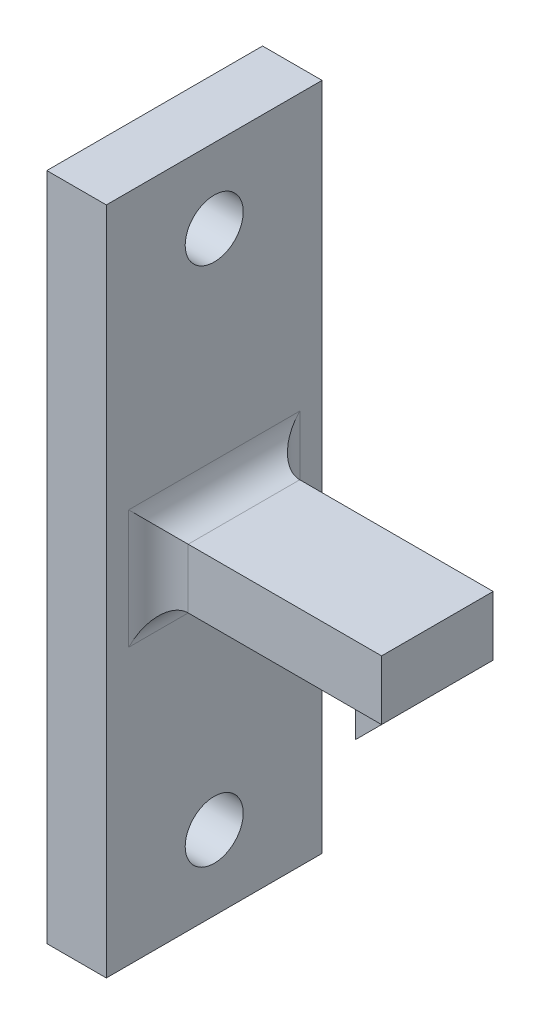
SolidWorks part; units mm, degrees
ref_plane "Front Plane" through (0, 0, 0) normal (0, 0, 1) x (1, 0, 0)
ref_plane "Top Plane" through (0, 0, 0) normal (0, 1, 0) x (1, 0, 0)
ref_plane "Right Plane" through (0, 0, 0) normal (1, 0, 0) x (0, 0, -1)
ref_plane "Plane1" through (0, 0, -2.5) normal (0, 0, 1) x (1, 0, 0)
sketch "Sketch2" plane through (0, 0, -2.5) normal (0, 0, 1) x (1, 0, 0)
  line L0 (230.0241, 2) -> (225.0241, 2)
  line L1 (225.0241, 2) -> (225.0241, -2)
  line L2 (225.0241, -2) -> (230.0241, -2)
  circle A0 centre (230.0241, 0) radius 1 construction
  circle A1 centre (230.0241, 0) radius 1
  circle A2 centre (230.0241, 0) radius 2
  dimension "D1" = 1
  dimension "D2" = 5
extrude "Boss-Extrude1" add sketch "Sketch2" along normal blind 1 and the other way blind 1 contours A2 L0 L1 L2 | A2 A1 region at (226.7677, 0, -2.5) region at (231.3983, 1.3742, -2.5)
sketch "Sketch3" plane through (0, 2, 0) normal (0, 1, 0) x (1, 0, 0)
  line L0 (225.0241, 1.5) -> (222.0241, -5.5)
  line L1 (222.0241, -5.5) -> (216.0955, -5.5)
  line L2 (216.0955, 10.5) -> (216.0955, 8.5)
  line L3 (216.0955, 10.5) -> (222.0241, 10.5)
  line L4 (225.0241, 3.5) -> (225.0241, 1.5)
  line L5 (225.0241, 1.5) -> (230.0241, 1.5)
  line L6 (230.0241, 1.5) -> (230.0241, 3.5)
  line L7 (230.0241, 3.5) -> (225.0241, 3.5)
  line L8 (225.0241, 3.5) -> (225.0241, 1.5)
  line L9 (225.0241, 1.5) -> (230.0241, 1.5)
  line L10 (230.0241, 1.5) -> (230.0241, 3.5)
  line L11 (230.0241, 3.5) -> (225.0241, 3.5)
  line L12 (222.0241, 10.5) -> (225.0241, 3.5)
  line L13 (216.0955, 8.5) -> (221.0955, 8.5)
  line L14 (221.0955, 8.5) -> (223.0241, 4)
  line L15 (223.0241, 4) -> (223.0241, 1)
  line L16 (230.0241, 2.5) -> (208.0852, 2.5) construction
  line L17 (139.7, 2.5) -> (266.7, 2.5) construction
  line L18 (216.0955, -5.5) -> (216.0955, -3.5)
  line L19 (221.0955, -3.5) -> (223.0241, 1)
  line L20 (216.0955, -3.5) -> (221.0955, -3.5)
  line M15 (225.0241, 3.5) -> (225.0241, 1.5)
  dimension "D2" = 2
  dimension "D3" = 5
  dimension "D4" = 2
  dimension "D5" = 7
  dimension "D6" = 3
  dimension "D7" = 3
  dimension "D1" = 0
extrude "Boss-Extrude2" add sketch "Sketch3" against normal up to surface (4 mm away) contours L16 L12 L3 L2 L13 L14 L15 M15 | L8 L16 L15 L19 L20 L18 L1 L0 region at (223.4139, 2, 1.9528) region at (224.0241, 2, -2.6199) up to face at (227.5241, -2, -2.5)
sketch "Sketch4" plane through (0, 0, -10.5) normal (0, 0, -1) x (-1, 0, 0)
  line L0 (-216.0955, 0) -> (-218.0955, 0)
  line L1 (-139.7, 0) -> (-266.7, 0) construction
  line L4 (-222.0241, -2) -> (-216.0955, -2)
  line L5 (-216.0955, -2) -> (-216.0955, 2)
  line L6 (-216.0955, 2) -> (-222.0241, 2)
  line L7 (-222.0241, 2) -> (-222.0241, -2)
  line L8 (-222.0241, -2) -> (-216.0955, -2)
  line L9 (-216.0955, -2) -> (-216.0955, 2)
  line L10 (-216.0955, 2) -> (-222.0241, 2)
  line L11 (-222.0241, 2) -> (-222.0241, -2)
  circle A0 centre (-218.0955, 0) radius 1.07
  dimension "D2" = 2.14
  dimension "D3" = 2
  dimension "D1" = 0
extrude "Cut-Extrude1" cut sketch "Sketch4" against normal through all contours A0 region at (219.1352, 0, -10.5)
sketch "Sketch6" plane through (0, 0, -1.5) normal (0, 0, 1) x (1, 0, 0)
  line L0 (230.0241, 2) -> (240.0241, 2)
  line L1 (240.0241, 2) -> (240.0241, -2)
  line L2 (240.0241, -2) -> (230.0241, -2)
  line L3 (230.0241, 2) -> (228.1025, 2)
  line L4 (230.0241, 2) -> (225.0241, 2) construction
  line L5 (228.1025, 2) -> (228.1025, -2)
  line L6 (225.0241, -2) -> (230.0241, -2) construction
  line L7 (228.1025, -2) -> (230.0241, -2)
  arc A0 (230.0241, -2) -> (230.0241, 2) centre (230.0241, 0) ccw construction
  dimension "D1" = 10
extrude "Boss-Extrude3" add sketch "Sketch6" against normal blind 2
sketch "Sketch8" plane through (0, 0, -3.5) normal (0, 0, -1) x (-1, 0, 0)
  line L0 (-240.0241, -2) -> (-236.0241, -6)
  line L1 (-240.0241, 2) -> (-236.0241, 2)
  line L2 (-240.0241, 2) -> (-240.0241, -6)
  line L3 (-240.0241, -6) -> (-236.0241, -6)
  line L4 (-236.0241, 2) -> (-236.0241, -6)
  dimension "D1" = 4
  dimension "D2" = 8
extrude "Boss-Extrude4" add sketch "Sketch8" against normal blind 2 contours L2 L1 L4 L3
sketch "Sketch9" plane through (0, 0, -3.5) normal (0, 0, -1) x (-1, 0, 0)
  line L0 (-236.0241, -6) -> (-240.0241, -6)
  line L1 (-240.0241, -6) -> (-240.0241, -2)
  line L2 (-240.0241, -6) -> (-240.0241, 2) construction
  line L3 (-240.0241, -2) -> (-236.0241, -6)
extrude "Cut-Extrude2" cut sketch "Sketch9" against normal blind 2
sketch "Sketch10" plane through (0, 0, -3.5) normal (0, 0, -1) x (-1, 0, 0)
  line L0 (-240.0241, -2) -> (-240.0241, 2) construction
  line L1 (-240.0241, -2) -> (-223.5241, -2)
  line L2 (-240.0241, -2) -> (-240.0241, 2)
  line L3 (-240.0241, 2) -> (-223.5241, 2)
  line L4 (-223.5241, -2) -> (-223.5241, 2)
  line L5 (-222.0241, 2) -> (-225.0241, 2) construction
extrude "Boss-Extrude5" add sketch "Sketch10" along normal blind 2.75
sketch "Sketch11" plane through (0, 0, -1.5) normal (0, 0, 1) x (1, 0, 0)
  line L0 (225.0241, -2) -> (222.0241, -2) construction
  line L1 (240.0241, 2) -> (223.5241, 2)
  line L2 (240.0241, 2) -> (240.0241, -2)
  line L3 (240.0241, -2) -> (223.5241, -2)
  line L4 (223.5241, 2) -> (223.5241, -2)
extrude "Boss-Extrude6" add sketch "Sketch11" along normal blind 2.75
sketch "Sketch12" plane through (0, 0, -3.5) normal (0, 0, -1) x (-1, 0, 0)
  line L0 (-240.0241, -2) -> (-236.0241, -6)
  line L1 (-236.0241, -6) -> (-236.0241, -2)
  line L2 (-236.0241, -2) -> (-240.0241, -2)
extrude "Boss-Extrude7" add sketch "Sketch12" along normal blind 0.5
sketch "Sketch13" plane through (0, 0, -1.5) normal (0, 0, 1) x (1, 0, 0)
  line L0 (236.0241, -2) -> (236.0241, -6)
  line L1 (236.0241, -6) -> (240.0241, -2)
  line L2 (240.0241, -2) -> (236.0241, -2)
extrude "Boss-Extrude8" add sketch "Sketch13" along normal blind 0.5
sketch "Sketch14" plane through (0, 0, -6.25) normal (0, 0, -1) x (-1, 0, 0)
  line L0 (-223.8455, 2) -> (-240.0241, 2) construction
  line L1 (-224.804, 2) -> (-223.0241, 2)
  line L2 (-224.804, 2) -> (-224.804, -2)
  line L3 (-224.804, -2) -> (-223.0241, -2)
  line L4 (-223.0241, 2) -> (-223.0241, -2)
extrude "Boss-Extrude9" add sketch "Sketch14" against normal up to surface (7.5 mm away) up to face at (231.9348, 0, 1.25)
sketch "Sketch15" plane through (223.0241, 0, 0) normal (-1, 0, 0) x (0, 0, 1)
  line L0 (-4, 2) -> (-1, -2) construction
  line L2 (-22.5, -13.6568) -> (17.5, -13.6568)
  line L3 (-22.5, -13.6568) -> (-22.5, 13.6568)
  line L4 (-22.5, 13.6568) -> (17.5, 13.6568)
  line L5 (17.5, -13.6568) -> (17.5, 13.6568)
  line L6 (-22.5, -13.6568) -> (17.5, 13.6568) construction
  line L7 (-22.5, 13.6568) -> (17.5, -13.6568) construction
  point P4 (-2.5, 0)
  dimension "D1" = 40
extrude "Cut-Extrude3" cut sketch "Sketch15" along normal blind 10 and the other way blind 2
sketch "Sketch16" plane through (225.0241, 0, 0) normal (-1, 0, 0) x (0, 0, 1)
  line L0 (-6.25, 2) -> (1.25, -2) construction
  line L1 (-6.25, -2) -> (1.25, 2) construction
  line L3 (-9.75, -22.5) -> (4.75, -22.5)
  line L4 (-9.75, -22.5) -> (-9.75, 22.5)
  line L5 (-9.75, 22.5) -> (4.75, 22.5)
  line L6 (4.75, -22.5) -> (4.75, 22.5)
  line L7 (-9.75, -22.5) -> (4.75, 22.5) construction
  line L8 (-9.75, 22.5) -> (4.75, -22.5) construction
  point P8 (-2.5, 0)
  dimension "D1" = 14.5
  dimension "D2" = 45
extrude "Boss-Extrude10" add sketch "Sketch16" along normal blind 4
sketch "Sketch18" plane through (221.0241, 0, 0) normal (-1, 0, 0) x (0, 0, 1)
  line L0 (-9.75, 22.5) -> (4.75, -22.5) construction
  line L1 (-9.75, -22.5) -> (4.75, 22.5) construction
  line L2 (4.75, 22.5) -> (-9.75, 22.5) construction
  line L3 (-9.75, -22.5) -> (4.75, -22.5) construction
  circle A0 centre (-2.5, 17.5) radius 1.95
  circle A1 centre (-2.5, -17.5) radius 1.95
  dimension "D3" = 3.9
  dimension "D4" = 3.9
  dimension "D1" = 5
  dimension "D2" = 5
extrude "Cut-Extrude4" cut sketch "Sketch18" against normal blind 4
fillet "Fillet1" radius 2 4 edges at (225.0241, -2, -2.5) (225.0241, 0, 1.25) (225.0241, 2, -2.5) (225.0241, 0, -6.25)
